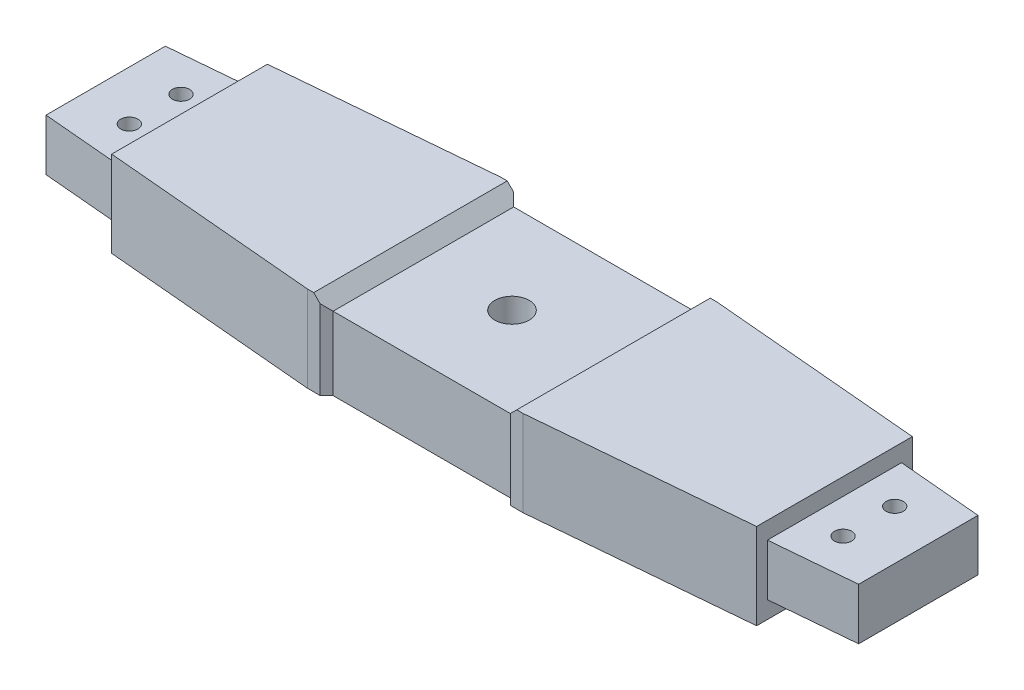
SolidWorks part; units mm, degrees
ref_plane "Front" through (0, 0, 0) normal (0, 0, 1) x (1, 0, 0)
ref_plane "Top" through (0, 0, 0) normal (0, 1, 0) x (1, 0, 0)
ref_plane "Right" through (0, 0, 0) normal (1, 0, 0) x (0, 0, -1)
sketch "Sketch1" plane through (0, 0, 0) normal (0, 1, 0) x (1, 0, 0)
  line L0 (0, 0) -> (0, 20) construction
  line L1 (-25, 20) -> (25, 20)
  line L2 (-161.6019, 7.9692) -> (-25, 20)
  line L3 (25, 20) -> (161.6019, 7.9692)
  line L4 (-160.9, 0) -> (160.9, 0) construction
  line L5 (-161.6019, -7.9692) -> (-25, -20)
  line L6 (-25, -20) -> (25, -20)
  line L7 (25, -20) -> (161.6019, -7.9692)
  line L9 (-95, -25) -> (95, -25)
  line L10 (-95, -25) -> (-95, 25)
  line L11 (-95, 25) -> (95, 25)
  line L12 (95, -25) -> (95, 25)
  line L13 (-95, -25) -> (95, 25) construction
  line L14 (-95, 25) -> (95, -25) construction
  circle A0 centre (0, 0) radius 4
  circle A1 centre (-160.9, 0) radius 4
  circle A2 centre (160.9, 0) radius 4
  circle A3 centre (160.9, 0) radius 8
  circle A4 centre (-160.9, 0) radius 8
  dimension "D1" = 8
  dimension "D2" = 8
  dimension "D3" = 8
  dimension "D6" = 160.9
  dimension "D7" = 160.9
  dimension "D8" = 20
  dimension "D9" = 50
  dimension "D10" = 50
  dimension "D11" = 190
  dimension "D4" = 4
  dimension "D5" = 4
extrude "Boss-Extrude1" add sketch "Sketch1" along normal blind 12 contours L7 L12 L3 L1 L2 L10 L5 L6 A0 region at (0, 0, -18.0584)
sketch "Sketch2" plane through (0, 12, 0) normal (0, 1, 0) x (1, 0, 0)
  line L8 (-75, 18.1061) -> (-75, -18.1061)
  line L9 (-95, -13.8349) -> (-95, 13.8349) construction
  line L10 (75, 18.1061) -> (75, -18.1061)
  line L11 (95, -13.8349) -> (95, 13.8349) construction
  line L16 (25.1099, -22.5) -> (97.5, -16.1244)
  line L17 (97.5, -16.1244) -> (97.5, 16.1244)
  line L18 (97.5, 16.1244) -> (25.1099, 22.5)
  line L19 (25.1099, 22.5) -> (-25.1099, 22.5)
  line L20 (-25.1099, 22.5) -> (-97.5, 16.1244)
  line L21 (-97.5, 16.1244) -> (-97.5, -16.1244)
  line L22 (-97.5, -16.1244) -> (-25.1099, -22.5)
  line L23 (-25.1099, -22.5) -> (25.1099, -22.5)
  line L24 (25.1099, -22.5) -> (97.5, -16.1244)
  line L25 (97.5, -16.1244) -> (97.5, 16.1244)
  line L26 (97.5, 16.1244) -> (25.1099, 22.5)
  line L27 (25.1099, 22.5) -> (-25.1099, 22.5)
  line L28 (-25.1099, 22.5) -> (-97.5, 16.1244)
  line L29 (-97.5, 16.1244) -> (-97.5, -16.1244)
  line L30 (-97.5, -16.1244) -> (-25.1099, -22.5)
  line L31 (-25.1099, -22.5) -> (25.1099, -22.5)
  circle M11 centre (0, 0) radius 4
  line M12 (25, -20) -> (95, -13.8349)
  line M14 (95, 13.8349) -> (25, 20)
  line M15 (25, 20) -> (-25, 20)
  line M16 (-25, 20) -> (-95, 13.8349)
  line M18 (-95, -13.8349) -> (-25, -20)
  line M19 (-25, -20) -> (25, -20)
  dimension "D2" = 20
  dimension "D3" = 20
  dimension "D1" = 2.5
extrude "Boss-Extrude2" add sketch "Sketch2" along normal blind 4 and the other way blind 16 contours L10 L8 M14 M15 M16 M18 M19 M12 M11 | L30 L31 L24 L10 L8 M12 M19 M18 | L27 L28 L8 L10 L26 M16 M15 M14 region at (-49.9232, 12, -18.8072) region at (-49.8638, 12, -16.2518) region at (-50.1317, 12, 19.294)
sketch "Sketch3" plane through (0, 0, 22.5) normal (0, 0, 1) x (1, 0, 0)
  line L0 (-25.1099, 16) -> (25.1099, 16) construction
  line L1 (-25.1099, 16) -> (25.1099, 16)
  line L2 (23.6099, 16) -> (20.6099, 13)
  line L3 (20.6099, 13) -> (-20.6099, 13)
  line L4 (-20.6099, 13) -> (-23.6099, 16)
  dimension "D1" = 1.5
  dimension "D2" = 45
  dimension "D3" = 45
  dimension "D4" = 3
  dimension "D5" = 1.5
extrude "Cut-Extrude1" cut sketch "Sketch3" against normal through all and the other way through all contours L4 L3 L2 L1 region at (0, 14.5339, 22.5)
sketch "Sketch6" plane through (0, 0, -22.5) normal (0, 0, -1) x (-1, 0, 0)
  line L1 (-25.1099, -4) -> (25.1099, -4) construction
  circle A0 centre (-10, 4.5) radius 2.05
  circle A1 centre (10, 4.5) radius 2.05
  dimension "D1" = 4.1
  dimension "D2" = 4.1
  dimension "D3" = 10
  dimension "D4" = 10
  dimension "D5" = 8.5
extrude "Cut-Extrude3" cut sketch "Sketch6" against normal blind 6.5
sketch "Sketch7" plane through (0, 0, 0) normal (0, -1, 0) x (1, 0, 0)
  line L0 (-75, -18.1061) -> (-75, 18.1061) construction
  line L1 (0, 0) -> (0, 22.5) construction
  line L2 (-25.1099, 22.5) -> (25.1099, 22.5) construction
  circle A0 centre (-83, -6) radius 2
  circle A1 centre (-83, 6) radius 2
  circle A2 centre (83, 6) radius 2
  circle A3 centre (83, -6) radius 2
  dimension "D1" = 4
  dimension "D2" = 4
  dimension "D3" = 8
  dimension "D4" = 6
  dimension "D5" = 6
extrude "Cut-Extrude4" cut sketch "Sketch7" against normal through all
sketch "Sketch8" plane through (0, -4, 0) normal (0, -1, 0) x (1, 0, 0)
  line L0 (-22.1099, -22.5) -> (-20.6099, -21)
  line L1 (25.1099, -22.5) -> (-25.1099, -22.5) construction
  line L2 (-20.6099, -21) -> (20.6099, -21)
  line L3 (20.6099, -21) -> (22.1099, -22.5)
  line L4 (0, 0) -> (4, 0) construction
  line L5 (-22.1099, -22.5) -> (22.1099, -22.5)
  line L6 (-22.1099, 22.5) -> (22.1099, 22.5)
  line L7 (20.6099, 21) -> (22.1099, 22.5)
  line L8 (-20.6099, 21) -> (20.6099, 21)
  line L9 (-22.1099, 22.5) -> (-20.6099, 21)
  circle A0 centre (0, 0) radius 4 construction
  dimension "D1" = 45
  dimension "D2" = 1.5
  dimension "D3" = 3
  dimension "D4" = 3
extrude "Cut-Extrude5" cut sketch "Sketch8" against normal through all and the other way through all
sketch "Sketch9" plane through (0, 12, 0) normal (0, 1, 0) x (1, 0, 0)
  line L0 (-94.5, 13.879) -> (-94.5, -13.879)
  line L1 (-95, 13.8349) -> (-75, 15.5964) construction
  line L2 (-95, -13.8349) -> (-75, -15.5964) construction
  line L3 (-95, -13.8349) -> (-95, 13.8349) construction
  line L4 (-94.5, 13.879) -> (-95, 13.8349)
  line L5 (-95, 13.8349) -> (-95, -13.8349)
  line L6 (-95, -13.8349) -> (-94.5, -13.879)
  line L7 (94.5, 13.879) -> (94.5, -13.879)
  line L8 (75, 15.5964) -> (95, 13.8349) construction
  line L9 (75, -15.5964) -> (95, -13.8349) construction
  line L10 (94.5, -13.879) -> (95, -13.8349)
  line L11 (95, -13.8349) -> (95, 13.8349)
  line L12 (95, 13.8349) -> (94.5, 13.879)
  dimension "D1" = 0.5
  dimension "D2" = 0.5
extrude "Cut-Extrude6" cut sketch "Sketch9" against normal through all
